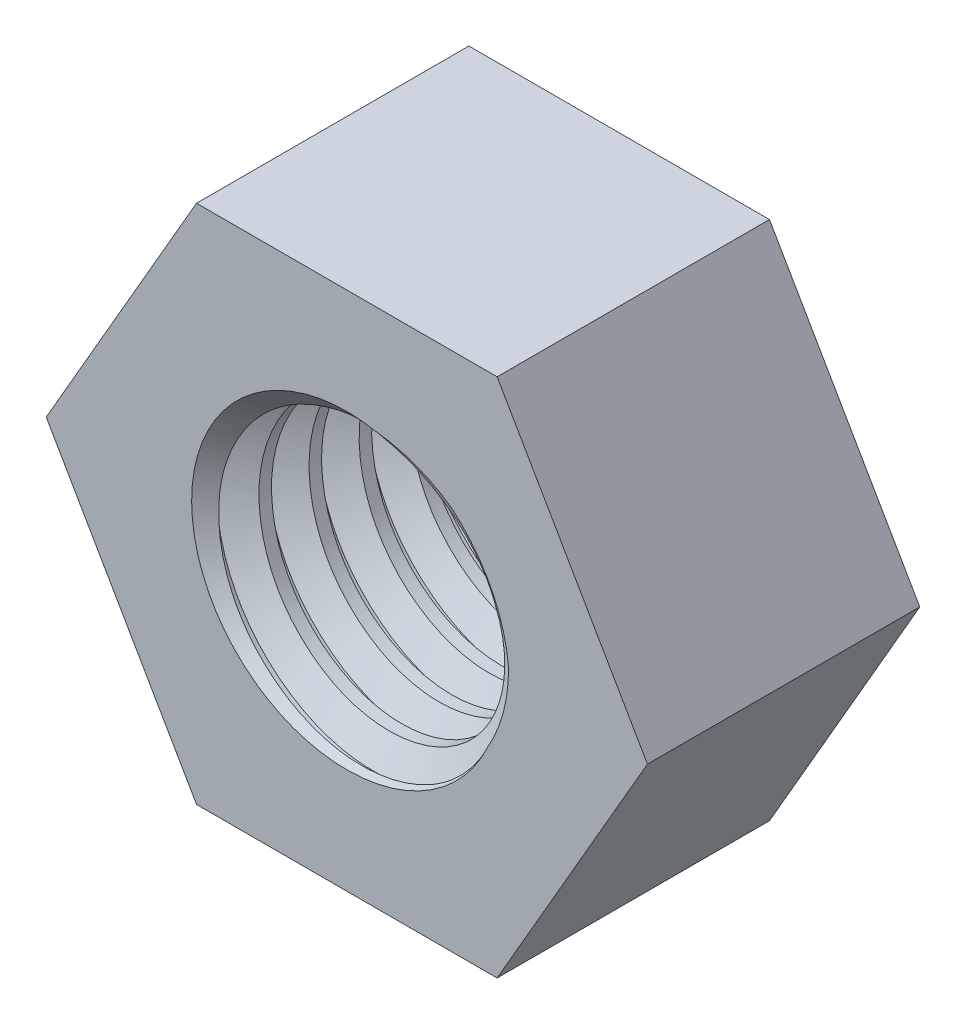
SolidWorks part; units mm, degrees
ref_plane "Plan de face" through (0, 0, 0) normal (0, 0, 1) x (1, 0, 0)
ref_plane "Plan de dessus" through (0, 0, 0) normal (0, 1, 0) x (1, 0, 0)
ref_plane "Plan de droite" through (0, 0, 0) normal (1, 0, 0) x (0, 0, -1)
sketch "Esquisse1" plane through (0, 0, 0) normal (0, 0, 1) x (1, 0, 0)
  line L1 (-3.7528, -6.5) -> (3.7528, -6.5)
  line L2 (3.7528, -6.5) -> (7.5056, 0)
  line L3 (7.5056, 0) -> (3.7528, 6.5)
  line L4 (3.7528, 6.5) -> (-3.7528, 6.5)
  line L5 (-3.7528, 6.5) -> (-7.5056, 0)
  line L6 (-7.5056, 0) -> (-3.7528, -6.5)
  circle A0 centre (0, 0) radius 6.5 construction
  circle A1 centre (0, 0) radius 3.375
  dimension "D2" = 6.75
  dimension "D1" = 13
extrude "Boss.-Extru.1" add sketch "Esquisse1" along normal blind 6.8
chamfer "Chanfrein1" distance 0.5 angle 45 2 edges at (3.375, 0, 0) (3.375, 0, 6.8)
thread "Filetage1" pitch 1.25 method cut trim with start face yes trim with end face yes profile "Profil de filetage1" start angle 0, offset 1, length 0, pitch 1.25, diameter 6.75
ref_plane "Plan1" through (-3.375, 0, 7.8) normal (0, -1, 0) x (-1, 0, 0)
sketch "Profil de filetage1" plane through (-3.375, 0, 7.8) normal (0, -1, 0) x (-1, 0, 0)
  line L0 (0, 0) -> (0, 1.25) construction
  line L1 (0, 0) -> (0.6766, 0.3906)
  line L2 (0.6766, 0.3906) -> (0.6766, 0.5469)
  line L3 (0.6766, 0.5469) -> (0, 0.9375)
  line L4 (0.6766, 0.4687) -> (0, 0.4687) construction
  line L11 (0, 0) -> (0, 0.9375)
  point P2 (0, 0)
  dimension "Pitch" = 1.25
  dimension "Profile_Angle" = 60
  dimension "Profile_Land" = 0.1562
  dimension "Profile_Height" = 0.6766
